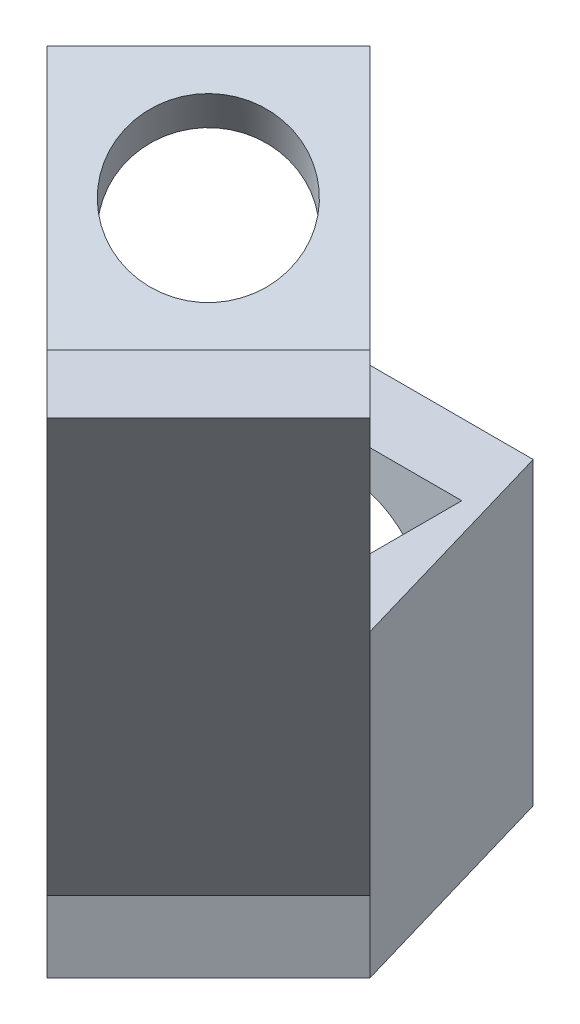
SolidWorks part; units mm, degrees
ref_plane "Front Plane" through (0, 0, 0) normal (0, 0, 1) x (1, 0, 0)
ref_plane "Top Plane" through (0, 0, 0) normal (0, 1, 0) x (1, 0, 0)
ref_plane "Right Plane" through (0, 0, 0) normal (1, 0, 0) x (0, 0, -1)
sketch "Sketch1" plane through (0, 0, 0) normal (0, 0, 1) x (1, 0, 0)
  line L1 (16, -16) -> (-16, -16)
  line L2 (16, -16) -> (16, 16)
  line L3 (16, 16) -> (-16, 16)
  line L4 (-16, -16) -> (-16, 16)
  line L5 (16, -16) -> (-16, 16) construction
  line L6 (16, 16) -> (-16, -16) construction
  circle A0 centre (0, 0) radius 11
  point P9 (20.6065, -6.9739)
  point P10 (21.8965, -5.332)
  dimension "D1" = 22
  dimension "D2" = 16
  dimension "D3" = 16
extrude "Boss-Extrude1" add sketch "Sketch1" along normal blind 10
sketch "Sketch2" plane through (0, -16, 0) normal (0, -1, 0) x (1, 0, 0)
  line L0 (0, 10) -> (0, 29.5) construction
  line L1 (-16, 10) -> (16, 10) construction
  line L2 (0, 29.5) -> (14.1421, 43.6421) construction
  line L3 (0, 29.5) -> (22.6274, 29.5) construction
  line L4 (-16, 10) -> (-16, 29.5)
  line L5 (16, 10) -> (16, 22.8726)
  line L6 (14.1421, 43.6421) -> (25.4558, 32.3284)
  line L7 (14.1421, 43.6421) -> (2.8284, 54.9558)
  line L9 (25.4558, 32.3284) -> (16, 22.8726)
  line L10 (-16, 29.5) -> (0, 29.5) construction
  line L11 (16, 10) -> (16, 0)
  line L12 (16, 0) -> (-16, 0)
  line L13 (-16, 0) -> (-16, 10)
  line L14 (2.8284, 54.9558) -> (-16, 36.1274)
  line L15 (-16, 29.5) -> (-16, 36.1274)
  point P11 (-16.2666, 35.8608)
  dimension "D1" = 19.5
  dimension "D2" = 20
  dimension "D3" = 45
  dimension "D4" = 16
  dimension "D5" = 16
  dimension "D6" = 90
  dimension "D7" = 90
extrude "Boss-Extrude2" add sketch "Sketch2" along normal blind 10
sketch "Sketch7" plane through (-3.4363, 0, 3.4363) normal (0.7071, 0, -0.7071) x (-0.7071, 0, -0.7071)
  line L0 (-40.8597, -16) -> (-121.1604, 98.6813)
  line L1 (-121.1604, 98.6813) -> (-109.4878, 98.6813)
  line L2 (-109.4878, 98.6813) -> (-29.1871, -16)
  line L3 (-27.4871, -16) -> (-40.8597, -16) construction
  line L4 (-40.8597, -16) -> (-29.1871, -16)
  point P8 (0, 0)
  dimension "D1" = 55
  dimension "D2" = 140
  dimension "D3" = 1.7
extrude "Boss-Extrude5" add sketch "Sketch7" against normal up to surface (32 mm away) contours L4 L2 L1 L0 up to face at (-6.5858, -21, 45.5416)
sketch "Sketch8" plane through (-3.4363, 0, 3.4363) normal (0.7071, 0, -0.7071) x (-0.7071, 0, -0.7071)
  line L0 (-109.4878, 98.6813) -> (-83.2749, 117.0357)
  line L1 (-109.4878, 98.6813) -> (-29.1871, -16) construction
  line L2 (-83.2749, 117.0357) -> (-77.5391, 108.8442)
  line L3 (-77.5391, 108.8442) -> (-103.752, 90.4898)
  line L4 (-103.752, 90.4898) -> (-109.4878, 98.6813)
  dimension "D1" = 32
  dimension "D2" = 10
extrude "Boss-Extrude6" add sketch "Sketch8" against normal up to surface (32 mm away) up to face at (11.3139, 13.9089, 63.4413)
sketch "Sketch9" plane through (58.2553, 117.6586, 58.2553) normal (0.4056, 0.8192, 0.4056) x (0.9141, -0.3635, -0.18)
  line L0 (-15.4487, -14.0585) -> (4.8293, -38.8134) construction
  line L1 (-27.8261, -24.1975) -> (-3.0713, -3.9195) construction
  line L2 (-7.5481, -48.9524) -> (17.2067, -28.6744) construction
  line L3 (-17.6871, -36.5749) -> (7.0677, -16.2969) construction
  line L4 (-7.5481, -48.9524) -> (-27.8261, -24.1975) construction
  line L5 (-3.0713, -3.9195) -> (17.2067, -28.6744) construction
  circle A0 centre (-5.3097, -26.4359) radius 11
  dimension "D1" = 22
extrude "Cut-Extrude2" cut sketch "Sketch9" against normal up to next
sketch "Sketch10" plane through (0, -26, 0) normal (0, -1, 0) x (1, 0, 0)
  line L0 (16, 0) -> (25.4558, 32.3284)
  line L1 (25.4558, 32.3284) -> (16, 22.8726)
  line L2 (16, 22.8726) -> (16, 0)
extrude "Boss-Extrude7" add sketch "Sketch10" against normal blind 42
